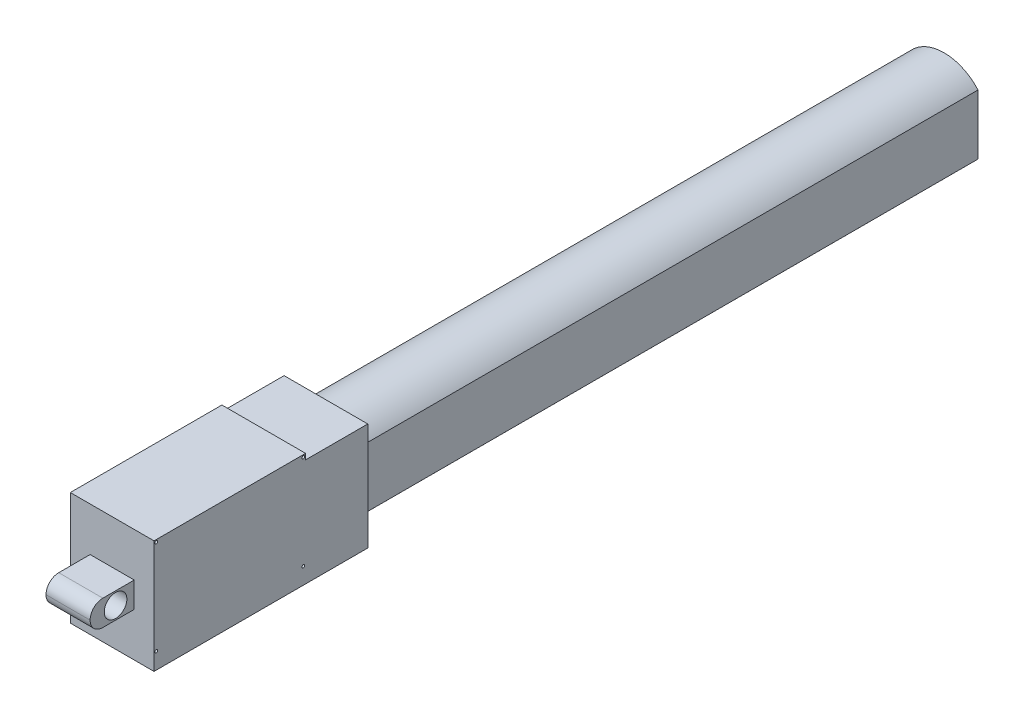
SolidWorks part; units mm, degrees
ref_plane "Front Plane" through (0, 0, 0) normal (0, 0, 1) x (1, 0, 0)
ref_plane "Top Plane" through (0, 0, 0) normal (0, 1, 0) x (1, 0, 0)
ref_plane "Right Plane" through (0, 0, 0) normal (1, 0, 0) x (0, 0, -1)
sketch "Sketch3" plane through (0, 0, 0) normal (0, 0, 1) x (1, 0, 0)
  line L2 (-3.05, -3.3087) -> (-3.05, 3.3087)
  line L4 (3.05, -3.3087) -> (3.05, 3.3087)
  line L6 (-6, -5.2915) -> (-6, 5.2915)
  line L8 (6, -5.2915) -> (6, 5.2915)
  arc A0 (-3.05, -3.3087) -> (3.05, -3.3087) centre (0, 0) ccw
  arc A1 (3.05, 3.3087) -> (-3.05, 3.3087) centre (0, 0) ccw
  arc A2 (-6, -5.2915) -> (6, -5.2915) centre (0, 0) ccw
  arc A3 (6, 5.2915) -> (-6, 5.2915) centre (0, 0) ccw
  point P0 (0, 0)
  dimension "D2" = 4.5
  dimension "D3" = 6.6174
  dimension "D6" = 8
  dimension "D1" = 6.1
  dimension "D4" = 12
  dimension "D5" = 10.583
extrude "Boss-Extrude2" add sketch "Sketch3" along normal blind 109.3
sketch "Sketch4" plane through (0, 0, 109.3) normal (0, 0, 1) x (1, 0, 0)
  line L0 (-3.05, 3.3087) -> (-3.05, -3.3087) construction
  line L1 (-7.4, -9.5) -> (7.4, -9.5)
  line L2 (-7.4, -9.5) -> (-7.4, 9.5)
  line L3 (-7.4, 9.5) -> (7.4, 9.5)
  line L4 (7.4, -9.5) -> (7.4, 9.5)
  line L5 (-7.4, -9.5) -> (7.4, 9.5) construction
  line L6 (-7.4, 9.5) -> (7.4, -9.5) construction
  line L7 (3.05, -3.3087) -> (3.05, 3.3087) construction
  line L8 (-3.05, 3.3087) -> (-3.05, -3.3087)
  line L9 (3.05, -3.3087) -> (3.05, 3.3087)
  arc A0 (3.05, 3.3087) -> (-3.05, 3.3087) centre (0, 0) ccw construction
  arc A1 (-3.05, -3.3087) -> (3.05, -3.3087) centre (0, 0) ccw construction
  arc A2 (-3.05, -3.3087) -> (3.05, -3.3087) centre (0, 0) ccw
  arc A3 (3.05, 3.3087) -> (-3.05, 3.3087) centre (0, 0) ccw
  point P0 (0, 0)
  dimension "D1" = 14.8
  dimension "D2" = 19
extrude "Boss-Extrude3" add sketch "Sketch4" along normal blind 11
sketch "Sketch5" plane through (0, 0, 120.3) normal (0, 0, 1) x (1, 0, 0)
  line L0 (-3.05, 3.3087) -> (-3.05, -3.3087) construction
  line L1 (-7.4, -9.5) -> (7.4, -9.5)
  line L2 (-7.4, -9.5) -> (-7.4, 10.5)
  line L3 (-7.4, 10.5) -> (7.4, 10.5)
  line L4 (7.4, -9.5) -> (7.4, 10.5)
  line L5 (-7.4, -9.5) -> (7.4, 10.5) construction
  line L6 (-7.4, 10.5) -> (7.4, -9.5) construction
  line L7 (3.05, -3.3087) -> (3.05, 3.3087) construction
  line L8 (-3.05, 3.3087) -> (-3.05, -3.3087)
  line L9 (3.05, -3.3087) -> (3.05, 3.3087)
  arc A0 (3.05, 3.3087) -> (-3.05, 3.3087) centre (0, 0) ccw construction
  arc A1 (-3.05, -3.3087) -> (3.05, -3.3087) centre (0, 0) ccw construction
  arc A2 (3.05, 3.3087) -> (-3.05, 3.3087) centre (0, 0) ccw
  arc A3 (-3.05, -3.3087) -> (3.05, -3.3087) centre (0, 0) ccw
  point P0 (0, 0.5)
  dimension "D1" = 14.8
  dimension "D2" = 20
  dimension "D3" = 0.5
extrude "Boss-Extrude4" add sketch "Sketch5" along normal blind 25.4
sketch "Sketch7" plane through (0, 0, 145.7) normal (0, 0, 1) x (1, 0, 0)
  line L0 (-7.4, -9.5) -> (7.4, -9.5) construction
  line L1 (-7.4, 10.5) -> (-7.4, -9.5) construction
  line L2 (7.4, -9.5) -> (7.4, 10.5) construction
  line L3 (7.4, 10.5) -> (-7.4, 10.5) construction
  line L4 (-7.4, -9.5) -> (7.4, -9.5)
  line L5 (-7.4, 10.5) -> (-7.4, -9.5)
  line L6 (7.4, -9.5) -> (7.4, 10.5)
  line L7 (7.4, 10.5) -> (-7.4, 10.5)
extrude "Boss-Extrude5" add sketch "Sketch7" along normal blind 1.4
sketch "Sketch8" plane through (0, 0, 147.1) normal (0, 0, 1) x (1, 0, 0)
  line L0 (7.4, 10.5) -> (-7.4, 10.5) construction
  line L1 (-3.9, -1.75) -> (3.9, -1.75)
  line L2 (-3.9, -1.75) -> (-3.9, 2.75)
  line L3 (-3.9, 2.75) -> (3.9, 2.75)
  line L4 (3.9, -1.75) -> (3.9, 2.75)
  line L5 (-3.9, -1.75) -> (3.9, 2.75) construction
  line L6 (-3.9, 2.75) -> (3.9, -1.75) construction
  line L7 (-7.4, 10.5) -> (-7.4, -9.5) construction
  point P0 (0, 0.5)
  dimension "D1" = 4.5
  dimension "D2" = 7.8
  dimension "D3" = 7.75
  dimension "D4" = 3.5
extrude "Boss-Extrude6" add sketch "Sketch8" along normal blind 7.8
sketch "Sketch9" plane through (-3.9, 0, 0) normal (-1, 0, 0) x (0, 0, 1)
  line L0 (154.9, 2.75) -> (154.9, -1.75) construction
  line L1 (154.9, 2.75) -> (147.1, 2.75) construction
  circle A0 centre (150.4, 0.5) radius 2
  dimension "D1" = 4
  dimension "D2" = 4.5
  dimension "D3" = 2.25
extrude "Cut-Extrude1" cut sketch "Sketch9" against normal through all
fillet "Fillet1" radius 2.25 2 edges at (0, -1.75, 154.9) (0, 2.75, 154.9)
sketch "Sketch10" plane through (-7.4, 0, 0) normal (-1, 0, 0) x (0, 0, 1)
  line L0 (120.3, 10.5) -> (120.3, 9.5) construction
  line L1 (147.1, 10.5) -> (120.3, 10.5) construction
  circle A1 centre (120.7, -6.6) radius 0.25
  circle A3 centre (146.7, -6.6) radius 0.25
  circle A4 centre (120.7, 10.1) radius 0.25
  circle A6 centre (146.7, 10.1) radius 0.25
  dimension "D1" = 0.5
  dimension "D2" = 0.4
  dimension "D3" = 0.4
  dimension "D4" = 26
  dimension "D5" = 16.7
extrude "Cut-Extrude2" cut sketch "Sketch10" against normal through all
sketch "Sketch11" plane through (0, 0, 147.1) normal (0, 0, 1) x (1, 0, 0)
  circle A0 centre (0, 0) radius 12.8456
